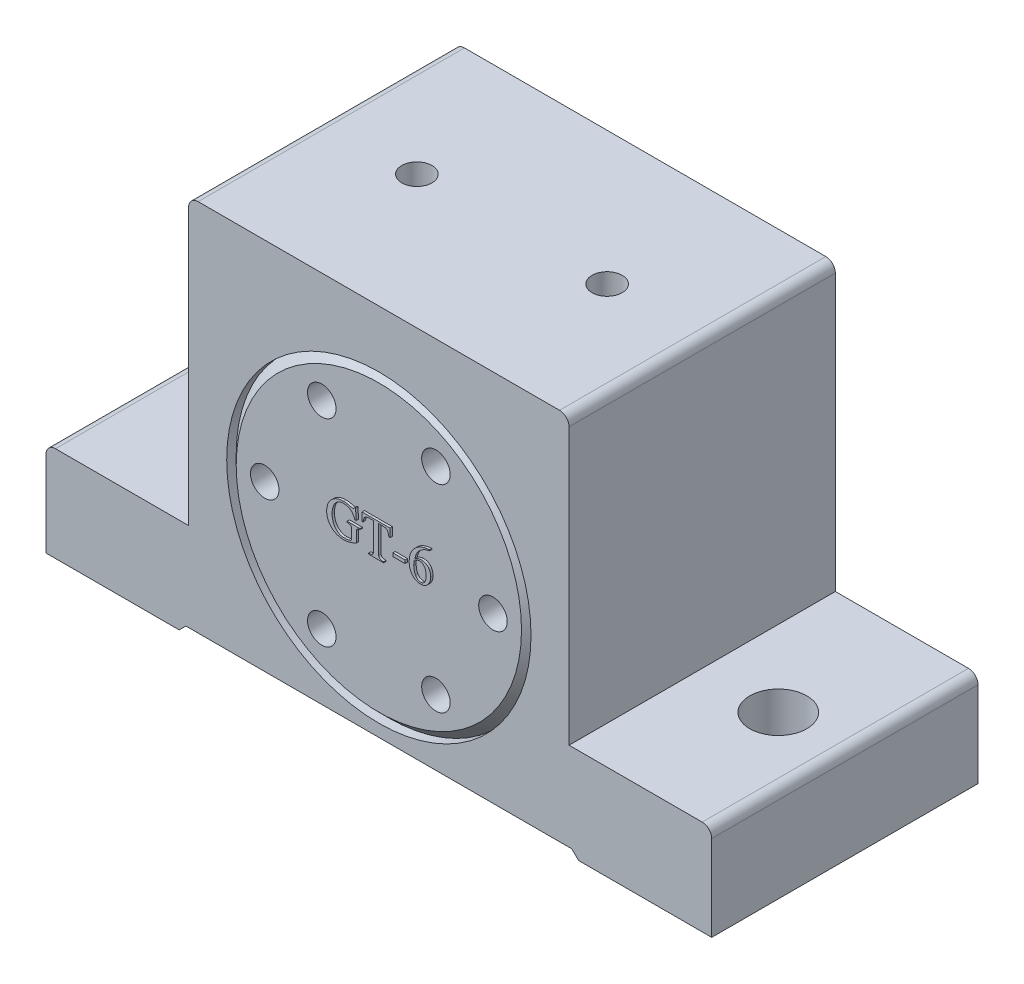
SolidWorks part; units mm, degrees
ref_plane "Front Plane" through (0, 0, 0) normal (0, 0, 1) x (1, 0, 0)
ref_plane "Top Plane" through (0, 0, 0) normal (0, 1, 0) x (1, 0, 0)
ref_plane "Right Plane" through (0, 0, 0) normal (1, 0, 0) x (0, 0, -1)
sketch "Sketch1" plane through (0, 0, 0) normal (0, 1, 0) x (1, 0, 0)
  line L1 (35, 14) -> (-35, 14)
  line L2 (35, 14) -> (35, -14)
  line L3 (35, -14) -> (-35, -14)
  line L4 (-35, 14) -> (-35, -14)
  line L5 (35, 14) -> (-35, -14) construction
  line L6 (35, -14) -> (-35, 14) construction
  point P0 (0, 0)
  dimension "D1" = 28
  dimension "D2" = 70
extrude "Boss-Extrude1" add sketch "Sketch1" along normal blind 10
sketch "Sketch2" plane through (0, 10, 0) normal (0, 1, 0) x (1, 0, 0)
  line L0 (-35, -14) -> (35, -14) construction
  line L1 (20, 14) -> (-20, 14)
  line L2 (20, 14) -> (20, -14)
  line L3 (20, -14) -> (-20, -14)
  line L4 (-20, 14) -> (-20, -14)
  line L5 (20, 14) -> (-20, -14) construction
  line L6 (20, -14) -> (-20, 14) construction
  point P0 (0, 0)
  dimension "D1" = 40
extrude "Boss-Extrude2" add sketch "Sketch2" along normal blind 30
sketch "Sketch3" plane through (0, 10, 0) normal (0, 1, 0) x (1, 0, 0)
  line L0 (28, 0) -> (-28, 0)
  point P4 (0, 0)
  dimension "D1" = 56
hole_wizard "Ø6.0mm Dowel Hole1" positions "Sketch4" profile "Sketch6" hole size "Ø6.0" standard "ISO" end condition through all
sketch "Sketch4" plane through (0, 10, 0) normal (0, 1, 0) x (1, 0, 0)
  point P0 (-28, 0)
  point P3 (28, 0)
sketch "Sketch6" plane through (-28, 10, 0) normal (1, 0, 0) x (0, 0, 1)
  line L0 (0, 0) -> (0, 10)
  line L1 (0, 10) -> (3, 10)
  line L2 (3, 10) -> (3, 0)
  line L5 (3, 0) -> (0, 0)
  line L11 (0, -6.35) -> (0, 107.95) construction
  dimension "Thru Hole Dia." = 6
  dimension "Thru Hole Depth" = 10
fillet "Fillet1" radius 1 2 edges at (35, 10, 0) (-35, 10, 0)
fillet "Fillet2" radius 1 2 edges at (20, 40, 0) (-20, 40, 0)
sketch "Sketch7" plane through (0, 40, 0) normal (0, 1, 0) x (1, 0, 0)
  line L0 (10, 0) -> (-10, 0) construction
  point P4 (0, 0)
  dimension "D1" = 20
hole_wizard "#6-32 Tapped Hole1" positions "Sketch8" profile "Sketch10" tap size "#6-32" standard "ANSI Inch"
sketch "Sketch8" plane through (0, 40, 0) normal (0, 1, 0) x (1, 0, 0)
  point P0 (-10, 0)
  point P3 (10, 0)
sketch "Sketch10" plane through (-10, 40, 0) normal (1, 0, 0) x (0, 0, 1)
  line L0 (0, 0) -> (0, 10.9539)
  line L1 (0, 10.9539) -> (1.5875, 10)
  line L2 (1.5875, 10) -> (1.5875, 0)
  line L5 (1.5875, 0) -> (0, 0)
  line L10 (0, 10.9539) -> (-1.5875, 10) construction
  line L11 (0, -6.35) -> (0, 107.95) construction
  dimension "Tap Drill Dia." = 3.175
  dimension "Tap Drill Depth" = 10
  dimension "Drill Angle" = 118
cosmetic thread "Hole Thread1" parameters "D1"=7.01, "D2"=3.5052
cosmetic thread "Hole Thread2" parameters "D1"=7.01, "D2"=3.5052
sketch "Sketch11" plane through (0, 0, 14) normal (0, 0, 1) x (1, 0, 0)
  line L0 (-35, 0) -> (35, 0) construction
  circle A0 centre (0, 18) radius 15
  circle A1 centre (0, 18) radius 16
  point P2 (0, 19.7757)
  dimension "D1" = 30
  dimension "D2" = 18
  dimension "D3" = 1
extrude "Cut-Extrude1" cut sketch "Sketch11" against normal blind 1
chamfer "Chamfer1" distance 1 angle 45 1 edges at (15, 18, 13)
sketch "Sketch13" plane through (0, 0, 14) normal (0, 0, 1) x (1, 0, 0)
  circle A0 centre (12, 18) radius 1.5
  circle A1 centre (6, 7.6077) radius 1.5
  circle A2 centre (-6, 7.6077) radius 1.5
  circle A3 centre (-12, 18) radius 1.5
  circle A4 centre (-6, 28.3923) radius 1.5
  circle A5 centre (6, 28.3923) radius 1.5
  circle A6 centre (0, 18) radius 15 construction
  point P15 (0, 18)
  dimension "D1" = 3
  dimension "D3" = 12
  dimension "D2" = 6
extrude "Cut-Extrude3" cut sketch "Sketch13" against normal blind 3
ref_plane "Plane1" through (0, 0, 0) normal (0, 0, 1) x (1, 0, 0)
sketch "Sketch14" plane through (0, 0, 14) normal (0, 0, 1) x (1, 0, 0)
  text T0 "GT-6" font "Romantic" height 3.5
extrude "Boss-Extrude3" add sketch "Sketch14" along normal blind 0.25
mirror "Mirror1" about plane through (0, 0, 0) normal (0, 0, 1) of "Cut-Extrude3", "Chamfer1", "Cut-Extrude1"
sketch "Sketch12" plane through (0, 0, 14) normal (0, 0, 1) x (1, 0, 0)
  line L0 (-21, 0) -> (-20.2929, 0.7071)
  line L1 (-35, 0) -> (35, 0) construction
  line L4 (-25, 0) -> (-25, 10) construction
  line L5 (0, 0) -> (0, 18.4078) construction
  line L6 (21, 0) -> (20.2929, 0.7071)
  line L7 (-20.2929, 0.7071) -> (20.2929, 0.7071)
  line L8 (-21, 0) -> (21, 0)
  dimension "D1" = 45
  dimension "D2" = 4
  dimension "D3" = 1
extrude "Cut-Extrude2" cut sketch "Sketch12" against normal through all
sketch "Sketch15" plane through (0, 0, -14) normal (0, 0, -1) x (-1, 0, 0)
  line L0 (-5.4906, 17.1109) -> (6.0415, 17.1109) construction
  text T0 "GT-6" font "Romantic" height 3.5
  point P4 (-6.768, 17.1109)
  point P5 (-4.9052, 17.1449)
  point P6 (-5.4906, 17.1109)
  point P7 (6.9641, 17.1109)
  point P8 (0, 0)
  point P9 (-4.62, 17.1109)
  point P10 (-4.62, 17.1109)
  point P11 (0, 0)
  point P12 (5.1899, 17.1109)
  point P13 (6.0415, 17.1109)
extrude "Boss-Extrude4" add sketch "Sketch15" along normal blind 0.25
